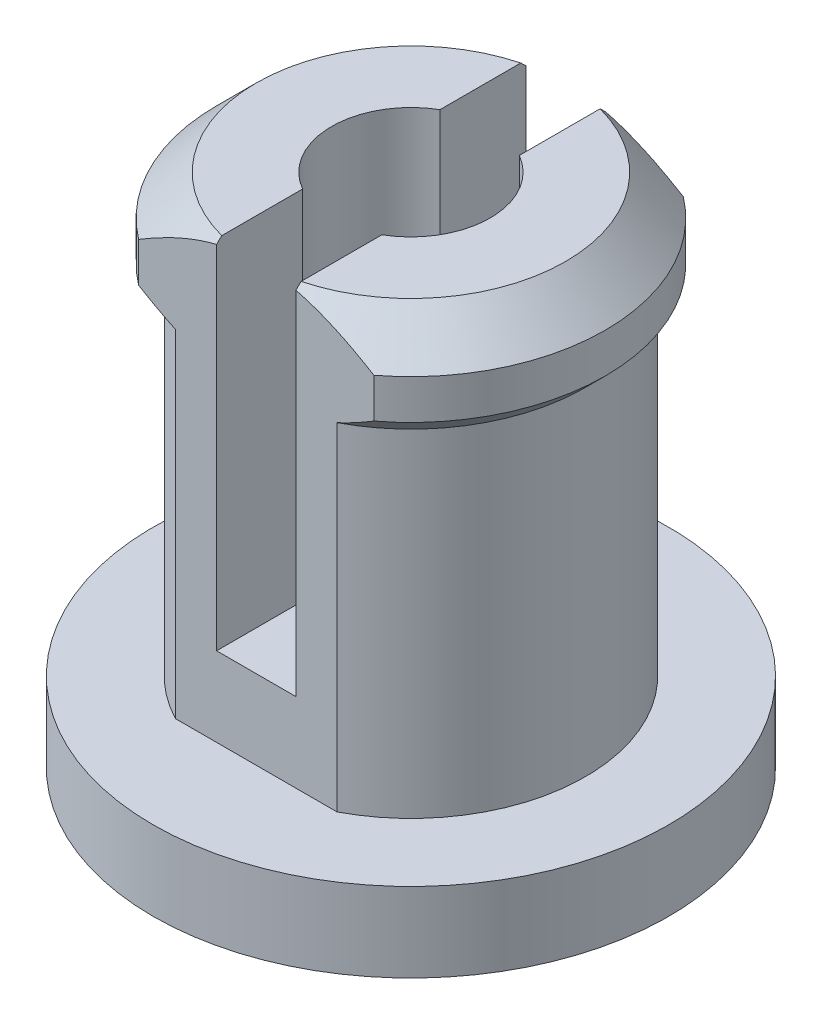
SolidWorks part; units mm, degrees
ref_plane "Plano frontal" through (0, 0, 0) normal (0, 0, 1) x (1, 0, 0)
ref_plane "Plano superior" through (0, 0, 0) normal (0, 1, 0) x (1, 0, 0)
ref_plane "Plano direito" through (0, 0, 0) normal (1, 0, 0) x (0, 0, -1)
sketch "Esboço1" plane through (0, 0, 0) normal (0, 1, 0) x (1, 0, 0)
  circle A0 centre (0, 0) radius 6.5
  dimension "D1" = 13
extrude "Ressalto-extrusão1" add sketch "Esboço1" against normal blind 2
sketch "Esboço2" plane through (0, 0, 0) normal (0, 1, 0) x (1, 0, 0)
  circle A0 centre (0, 0) radius 4.4
  dimension "D1" = 8.8
extrude "Ressalto-extrusão2" add sketch "Esboço2" along normal blind 8
sketch "Esboço3" plane through (0, 8, 0) normal (0, 1, 0) x (1, 0, 0)
  circle A0 centre (0, 0) radius 4.9
  circle A1 centre (0, 0) radius 4.4 construction
  circle A2 centre (0, 0) radius 4.4 construction
  dimension "D1" = 9.8
  dimension "D2" = 8.8
extrude "Ressalto-extrusão3" add sketch "Esboço3" along normal blind 3
sketch "Esboço4" plane through (0, 11, 0) normal (0, 1, 0) x (1, 0, 0)
  line L0 (-2.9665, 3.9) -> (2.9665, 3.9)
  line L1 (0, 0) -> (2.2669, 0) construction
  line L2 (-2.9665, -3.9) -> (2.9665, -3.9)
  circle A1 centre (0, 0) radius 4.9 construction
  circle A2 centre (0, 0) radius 4.9 construction
  circle M4 centre (0, 0) radius 4.9
  dimension "D1" = 4.9
  dimension "D2" = 3.9
extrude "Corte-extrusão1" cut sketch "Esboço4" against normal up to surface (11 mm away) contours L2 M4 | L0 M4 region at (0, 11, -4.3037) region at (0, 11, 4.3037) up to face at (0, 0, 4.4)
sketch "Esboço5" plane through (0, 11, 0) normal (0, 1, 0) x (1, 0, 0)
  line L0 (0, 3.9) -> (0, -3.9) construction
  line L1 (2.0372, -3.9) -> (-2.0372, -3.9) construction
  line L2 (-1, 3.9) -> (-1, -3.9)
  line L3 (1, 3.9) -> (1, -3.9)
  circle A0 centre (0, 0) radius 2
  point P7 (0, 0)
  line M3 (-2.9665, -3.9) -> (2.9665, -3.9)
  line M5 (2.9665, 3.9) -> (-2.9665, 3.9)
  dimension "D3" = 4
  dimension "D1" = 1
  dimension "D2" = 1
extrude "Corte-extrusão2" cut sketch "Esboço5" against normal blind 9 contours L0 L2 A0 M5 | L0 A0 L3 M5 | L0 A0 L2 M3 | A0 L0 L3 M3 | L0 A0 L2 | A0 L0 L3 | L2 A0 | L3 A0 region at (0.5111, 11, -2.905) region at (-0.5111, 11, -2.905) region at (0.4885, 11, 0) region at (-0.4885, 11, 0) region at (0.5111, 11, 2.905) region at (-0.5111, 11, 2.905) region at (1.41, 11, 0) region at (-1.41, 11, 0)
chamfer "Chanfro1" distance 1 angle 45 4 edges at (-4.9, 8, 0) (-4.9, 11, 0) (4.9, 8, 0) (4.9, 11, 0)
equation "\"D1@Esboço3\"=\"D2@Esboço3\"+1"
equation "\"D2@Esboço4\"=\"D1@Esboço4\"-1"
